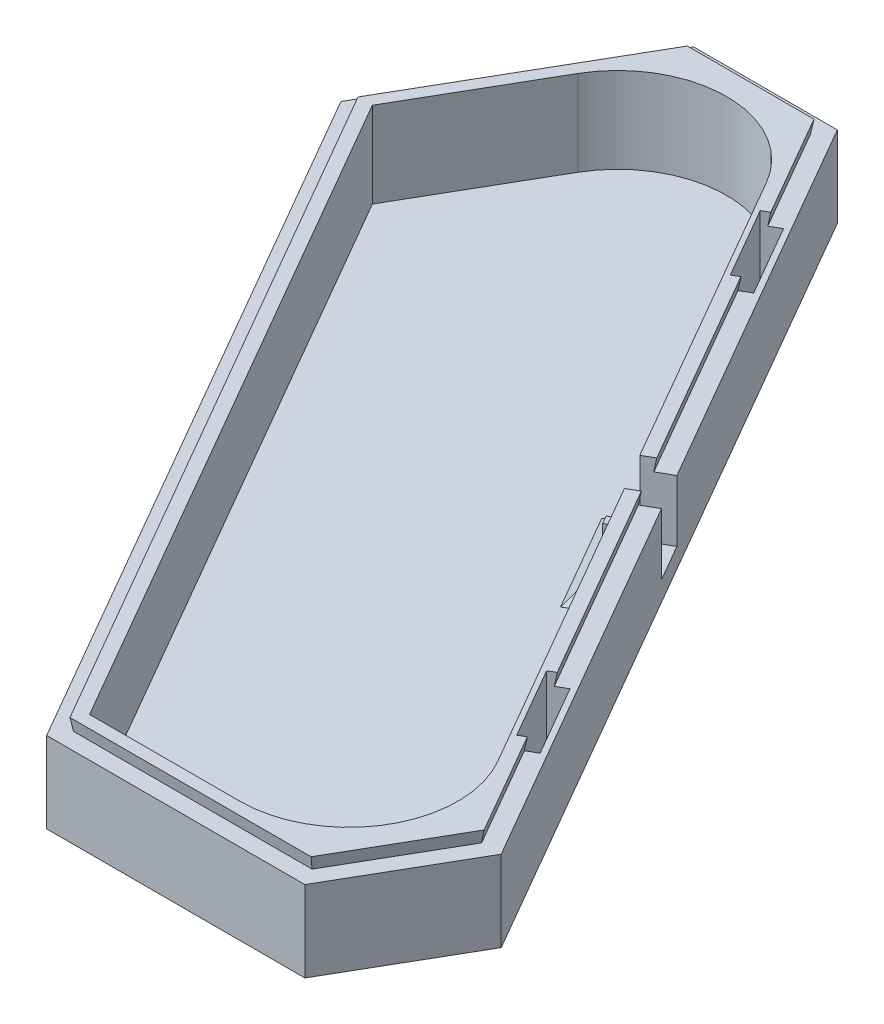
SolidWorks part; units mm, degrees
ref_plane "Plan de face" through (0, 0, 0) normal (0, 0, 1) x (1, 0, 0)
ref_plane "Plan de dessus" through (0, 0, 0) normal (0, 1, 0) x (1, 0, 0)
ref_plane "Plan de droite" through (0, 0, 0) normal (1, 0, 0) x (0, 0, -1)
sketch "Esquisse1" plane through (0, 0, 0) normal (0, 1, 0) x (1, 0, 0)
  line L3 (-77.5, -44.7446) -> (77.5, -44.7446)
  line L4 (77.5, -44.7446) -> (0, 89.4893)
  line L5 (0, 89.4893) -> (-77.5, -44.7446)
  line L6 (0, 89.4893) -> (0, -44.7446) construction
  line L7 (77.5, -44.7446) -> (-38.75, 22.3723) construction
  dimension "D1" = 155
extrude "Boss.-Extru.1" add sketch "Esquisse1" along normal blind 12 separate body
ref_axis "Axe1" through (0, -0.9, 0) along (0, 1, 0)
sketch "Esquisse2" plane through (0, 12, 0) normal (0, 1, 0) x (1, 0, 0)
  line L0 (-9.2376, 73.4893) -> (9.2376, 73.4893)
  line L1 (0, 89.4893) -> (-77.5, -44.7446) construction
  line L2 (77.5, -44.7446) -> (0, 89.4893) construction
  line L3 (9.2376, 73.4893) -> (0, 89.4893)
  line L4 (0, 89.4893) -> (-9.2376, 73.4893)
  line L5 (77.5, -44.7446) -> (68.2624, -28.7446)
  line L6 (68.2624, -28.7446) -> (59.0248, -44.7446)
  line L7 (59.0248, -44.7446) -> (77.5, -44.7446)
  line L8 (-77.5, -44.7446) -> (25.8333, -44.7446)
  line L9 (25.8333, -44.7446) -> (-25.8333, 44.7446)
  line L10 (-25.8333, 44.7446) -> (-77.5, -44.7446)
  line L11 (-77.5, -44.7446) -> (77.5, -44.7446) construction
  point P6 (0, 73.4893)
  point P17 (0, 0)
  dimension "D1" = 16
  dimension "D3" = 16
extrude "Enlèv. mat.-Extru.1" cut sketch "Esquisse2" against normal through all
sketch "Esquisse3" plane through (0, 12, 0) normal (0, 1, 0) x (1, 0, 0)
  line L3 (12.1244, 61.4893) -> (-12.1244, 61.4893) construction
  line L4 (59.3135, -20.2446) -> (12.1244, 61.4893)
  line L5 (-12.1244, 61.4893) -> (-21.7919, 44.7446)
  line L10 (-9.2376, 73.4893) -> (9.2376, 73.4893) construction
  line L11 (27.8541, -41.2446) -> (47.1891, -41.2446)
  line L12 (59.0132, -34.7407) -> (-47.6968, 28.0788) construction
  line L13 (0, -41.6074) -> (0, 68.4893) construction
  line L14 (47.9131, 27.5989) -> (-59.0132, -34.7407) construction
  line L15 (-9.2376, 73.4893) -> (-25.8333, 44.7446) construction
  line L16 (68.2624, -28.7446) -> (9.2376, 73.4893) construction
  line L17 (25.8333, -44.7446) -> (59.0248, -44.7446) construction
  line L18 (27.8541, -41.2446) -> (-21.7919, 44.7446)
  line L20 (25.8333, -44.7446) -> (-25.8333, 44.7446) construction
  arc A3 (12.1244, 61.4893) -> (-12.1244, 61.4893) centre (0, 54.4893) ccw
  arc A4 (47.1891, -41.2446) -> (59.3135, -20.2446) centre (47.1891, -27.2446) ccw
  arc A6 (-59.3135, -20.2446) -> (-59.0132, -34.7407) centre (-47.1891, -27.2446) ccw [skipped]
  point P23 (0, 0)
  dimension "D2" = 14
  dimension "D1" = 3.5
  dimension "D4" = 3.5
  dimension "D5" = 3.5
  dimension "D6" = 3.5
  dimension "D3" = 3
extrude "Enlèv. mat.-Extru.2" cut sketch "Esquisse3" against normal blind 11
sketch "Esquisse4" plane through (0, 12, 0) normal (0, 1, 0) x (1, 0, 0)
  line L0 (37.0689, 18.2841) -> (34.3689, 22.9606)
  line L1 (59.3135, -20.2446) -> (12.1244, 61.4893) construction
  line L2 (34.3689, 22.9606) -> (37.4, 24.7106)
  line L3 (68.2624, -28.7446) -> (9.2376, 73.4893) construction
  line L4 (37.4, 24.7106) -> (40.1, 20.0341)
  line L5 (40.1, 20.0341) -> (37.0689, 18.2841)
  point P9 (38.75, 22.3723)
  point P10 (38.75, 22.3723)
  point P21 (0, 0)
  dimension "D1" = 5.4
extrude "Enlèv. mat.-Extru.3" cut sketch "Esquisse4" against normal blind 9.5
ref_plane "Plan4" through (0, 0, 0) normal (0.5, 0, 0.866) x (0.866, 0, -0.5)
ref_plane "Plan5" through (0, 6.5, 0) normal (0, 1, 0) x (1, 0, 0)
sketch "Esquisse14" plane through (0, 1, 0) normal (0, 1, 0) x (1, 0, 0)
  line L4 (34.3689, 22.9606) -> (37.0689, 18.2841) construction
  line L5 (35.7189, 20.6223) -> (35.1993, 20.3223) construction
  line L6 (59.3135, -20.2446) -> (12.1244, 61.4893) construction
  line L7 (32.6993, 24.6524) -> (37.6993, 15.9922)
  line L8 (32.6993, 24.6524) -> (30.9672, 23.6524)
  line L9 (37.6993, 15.9922) -> (35.9672, 14.9922)
  line L10 (30.9672, 23.6524) -> (35.9672, 14.9922)
  line L11 (59.3135, -20.2446) -> (12.1244, 61.4893) construction
  dimension "D1" = 10
  dimension "D2" = 2
  dimension "D3" = 0.6
extrude "Boss.-Extru.6" add sketch "Esquisse14" along normal blind 2.2
sketch "Esquisse19" plane through (0, 2.5, 0) normal (0, 1, 0) x (1, 0, 0)
  line L0 (34.3689, 22.9606) -> (37.0689, 18.2841)
  line L1 (34.3689, 22.9606) -> (33.8493, 22.6606)
  line L2 (37.0689, 18.2841) -> (36.5493, 17.9841)
  line L3 (33.8493, 22.6606) -> (36.5493, 17.9841)
  line L4 (37.6993, 15.9922) -> (32.6993, 24.6524) construction
extrude "Boss.-Extru.8" add sketch "Esquisse19" against normal up to surface (1.5 mm away) up to face at (19.7712, 1, -11.4149)
sketch "Esquisse15" plane through (0, 3.2, 0) normal (0, 1, 0) x (1, 0, 0)
  line L0 (35.1591, 20.9919) -> (35.7591, 19.9527)
  line L1 (35.1591, 20.9919) -> (33.1672, 19.8419)
  line L2 (35.7591, 19.9527) -> (33.7672, 18.8027)
  line L3 (33.1672, 19.8419) -> (33.7672, 18.8027)
  line L5 (30.9672, 23.6524) -> (35.9672, 14.9922) construction
  line L8 (37.6993, 15.9922) -> (32.6993, 24.6524) construction
  line L9 (35.4591, 20.4723) -> (35.1993, 20.3223) construction
  dimension "D1" = 1.2
  dimension "D2" = 0.3
extrude "Boss.-Extru.7" add sketch "Esquisse15" along normal blind 3 and the other way up to surface (2.2 mm away) other way up to face at (28.414, 1, -16.4048)
chamfer "Chanfrein3" distance 2.2 angle 45 3 edges at (33.4672, 1, -19.3223) (36.8333, 1, -15.4922) (31.8333, 1, -24.1524)
sketch "Esquisse17" plane through (0, 12, 0) normal (0, 1, 0) x (1, 0, 0)
  line L0 (37.4, 24.7106) -> (9.2376, 73.4893) construction
  line L1 (-9.2376, 73.4893) -> (9.2376, 73.4893) construction
  line L2 (-9.2376, 73.4893) -> (-25.8333, 44.7446) construction
  line L3 (-9.2376, 73.4893) -> (-25.8333, 44.7446) construction
  line L4 (25.8333, -44.7446) -> (-25.8333, 44.7446) construction
  line L5 (25.8333, -44.7446) -> (59.0248, -44.7446) construction
  line L6 (25.8333, -44.7446) -> (59.0248, -44.7446) construction
  line L7 (68.2624, -28.7446) -> (59.0248, -44.7446) construction
  line L8 (68.2624, -28.7446) -> (40.1, 20.0341) construction
  line L9 (37.4, 24.7106) -> (9.2376, 73.4893)
  line L10 (-9.2376, 73.4893) -> (9.2376, 73.4893)
  line L11 (-9.2376, 73.4893) -> (-25.8333, 44.7446)
  line L12 (-9.2376, 73.4893) -> (-25.8333, 44.7446)
  line L13 (25.8333, -44.7446) -> (-25.8333, 44.7446)
  line L14 (25.8333, -44.7446) -> (59.0248, -44.7446)
  line L15 (25.8333, -44.7446) -> (59.0248, -44.7446)
  line L16 (68.2624, -28.7446) -> (59.0248, -44.7446)
  line L17 (68.2624, -28.7446) -> (40.1, 20.0341)
extrude "Enlèv. de mat.-Extru.-Mince1" cut sketch "Esquisse17" against normal blind 1.6 draft 10 thin draft outward yes thin type one direction reverse wall 1.9
sketch "Esquisse18" plane through (0, 12, 0) normal (0, 1, 0) x (1, 0, 0)
  line L0 (38.75, 22.3723) -> (0, 0) construction
  line L5 (9.2376, 73.4893) -> (37.4, 24.7106) construction
  line L6 (57.6135, -16.1003) -> (59.5188, -15.0003)
  line L7 (40.1, 20.0341) -> (37.4, 24.7106) construction
  line L8 (54.2688, -5.907) -> (59.5188, -15.0003)
  line L21 (52.3635, -7.007) -> (54.2688, -5.907)
  line L22 (20.1135, 48.8516) -> (14.8635, 57.9449)
  line L23 (20.1135, 48.8516) -> (22.0188, 49.9516)
  line L24 (22.0188, 49.9516) -> (16.7688, 59.0449)
  line L25 (14.8635, 57.9449) -> (16.7688, 59.0449)
  line L30 (52.3635, -7.007) -> (57.6135, -16.1003)
  point P4 (19.3938, 54.4983)
  dimension "D1" = 75
  dimension "D2" = 2.2
  dimension "D3" = 10.5
  dimension "D4" = 0.7
extrude "Enlèv. mat.-Extru.10" cut sketch "Esquisse18" against normal up to surface (11 mm away) up to face at (28.1419, 1, -16.2477)
sketch "Esquisse16" plane through (0, 0, 0) normal (0, 1, 0) x (1, 0, 0)
  line L0 (11.2217, 27.4997) -> (41.3465, -26.6864)
  line L1 (-19.3685, 82.5231) -> (-119.2403, 26.9993)
  line L2 (72.2349, -82.2461) -> (-27.6369, -137.7698)
  line L3 (-119.2403, 26.9993) -> (-27.6369, -137.7698)
  line L4 (-19.3685, 82.5231) -> (51.5403, 121.9449)
  line L6 (51.5403, 121.9449) -> (82.1306, 66.9215)
  line L7 (11.2217, 27.4997) -> (82.1306, 66.9215)
  line L8 (72.2349, -82.2461) -> (117.9546, -56.8282)
  line L10 (117.9546, -56.8282) -> (87.0662, -1.2686)
  line L11 (41.3465, -26.6864) -> (87.0662, -1.2686)
extrude "Enlèv. mat.-Extru.9" [suppressed] cut sketch "Esquisse16" along normal through all
equation "\"D6@Esquisse3\"=\"D4@Esquisse3\""
equation "\"D1@Esquisse3\"=\"D4@Esquisse3\""
